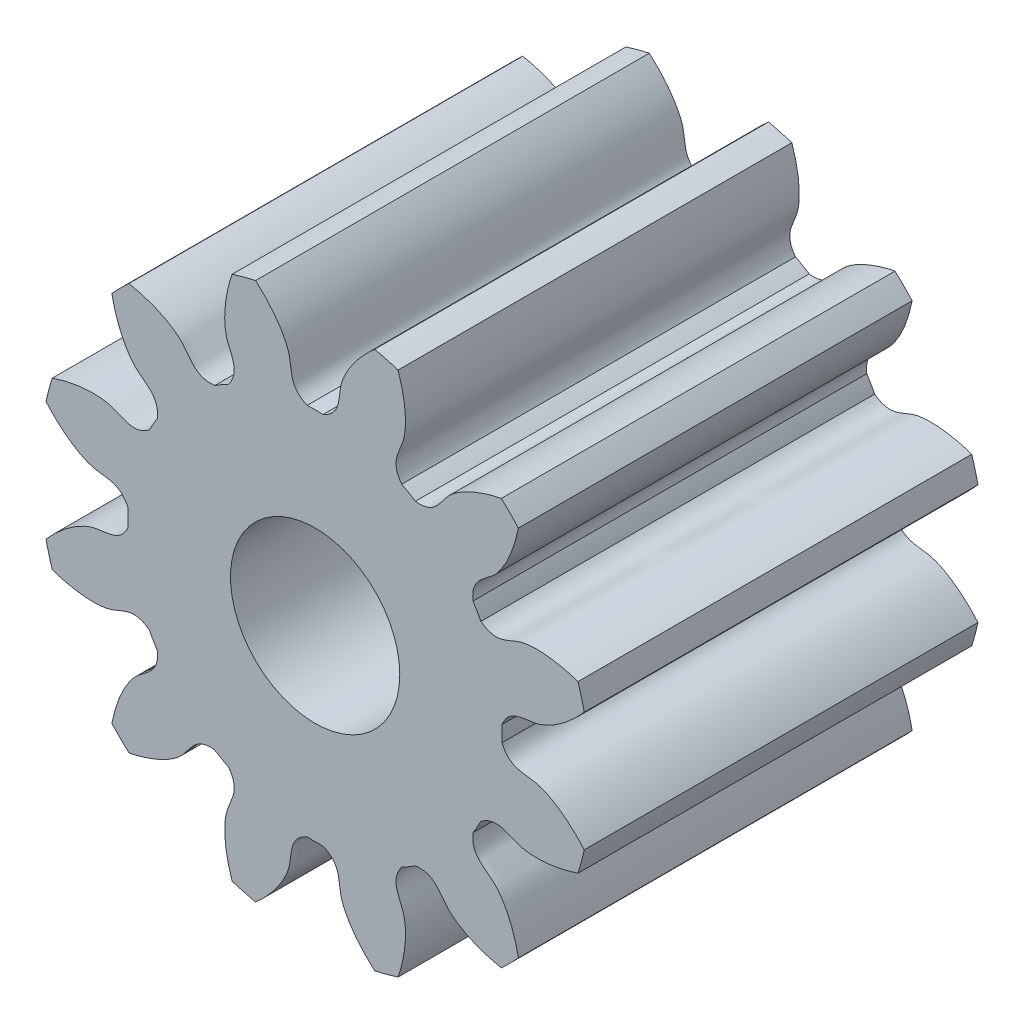
SolidWorks part; units mm, degrees
ref_plane "前视基准面" through (0, 0, 0) normal (0, 0, 1) x (1, 0, 0)
ref_plane "上视基准面" through (0, 0, 0) normal (0, 1, 0) x (1, 0, 0)
ref_plane "右视基准面" through (0, 0, 0) normal (1, 0, 0) x (0, 0, -1)
other "Configuration Table"
sketch "草图1" plane through (0, 0, 0) normal (0, 0, 1) x (1, 0, 0)
  circle A0 centre (0, 0) radius 3.5
extrude "凸台-拉伸1" add sketch "草图1" along normal blind 5
ref_axis "基准轴1" through (0, 0, 5) along (0, 0, -1)
sketch "草图2" plane through (0, 0, 0) normal (0, 0, 1) x (1, 0, 0)
  line L0 (0, 0) -> (0, 3.5) construction
  circle A0 centre (0, 0) radius 3.5 construction
  arc A1 (0.1004, 2.3729) -> (-0.1004, 2.3729) centre (0, 0) ccw
  arc A2 (1.7488, 3.9475) -> (-1.7488, 3.9475) centre (0, 0) ccw
  spline S0 degree 3 poles (0.1004, 2.3729) (0.3404, 2.4747) (0.2872, 2.6724) (0.3381, 2.8447) (0.3413, 2.855) (0.3451, 2.8662) (0.3495, 2.8784) (0.3546, 2.8915) (0.3603, 2.9056) (0.3668, 2.9206) (0.374, 2.9366) (0.3821, 2.9533) (0.3909, 2.971) (0.4007, 2.9894) (0.4114, 3.0086) (0.423, 3.0286) (0.4356, 3.0493) (0.4492, 3.0707) (0.4639, 3.0928) (0.4796, 3.1155) (0.4965, 3.1388) (0.5145, 3.1626) (0.5337, 3.187) (0.554, 3.2119) (0.5756, 3.2372) (0.5985, 3.2629) (0.6226, 3.289) (0.648, 3.3154) (0.6748, 3.342) (0.7028, 3.369) (0.7323, 3.3961) (0.7631, 3.4234) (0.7954, 3.4507) (0.829, 3.4782) (0.8641, 3.5057) (0.9006, 3.5331) (0.9385, 3.5604) (0.978, 3.5877) (1.0189, 3.6147) (1.0613, 3.6416) (1.1052, 3.6681) (1.1506, 3.6944) (1.1975, 3.7203) (1.2459, 3.7457) (1.2958, 3.7707) (1.3472, 3.7952) (1.4001, 3.8191) (1.4546, 3.8424) (1.5105, 3.865) (1.5679, 3.8869) (1.6472, 3.9154) (1.7078, 3.9351) (1.7488, 3.9475) knots 0 0 0 0 0.218015 0.222044 0.226546 0.231522 0.236972 0.242897 0.249295 0.256167 0.263513 0.271332 0.279626 0.288394 0.297636 0.307351 0.317541 0.328204 0.339341 0.350953 0.363038 0.375597 0.38863 0.402137 0.416118 0.430573 0.445502 0.460904 0.476781 0.493132 0.509956 0.527255 0.545027 0.563273 0.581994 0.601188 0.620856 0.640998 0.661614 0.682704 0.704268 0.726305 0.748817 0.771803 0.795262 0.819196 0.843603 0.868484 0.89384 0.919669 0.945972 1 1 1 1
  spline S1 degree 3 poles (-0.1004, 2.3729) (-0.3404, 2.4747) (-0.2872, 2.6724) (-0.3381, 2.8447) (-0.3413, 2.855) (-0.3451, 2.8662) (-0.3495, 2.8784) (-0.3546, 2.8915) (-0.3603, 2.9056) (-0.3668, 2.9206) (-0.374, 2.9366) (-0.3821, 2.9533) (-0.3909, 2.971) (-0.4007, 2.9894) (-0.4114, 3.0086) (-0.423, 3.0286) (-0.4356, 3.0493) (-0.4492, 3.0707) (-0.4639, 3.0928) (-0.4796, 3.1155) (-0.4965, 3.1388) (-0.5145, 3.1626) (-0.5337, 3.187) (-0.554, 3.2119) (-0.5756, 3.2372) (-0.5985, 3.2629) (-0.6226, 3.289) (-0.648, 3.3154) (-0.6748, 3.342) (-0.7028, 3.369) (-0.7323, 3.3961) (-0.7631, 3.4234) (-0.7954, 3.4507) (-0.829, 3.4782) (-0.8641, 3.5057) (-0.9006, 3.5331) (-0.9385, 3.5604) (-0.978, 3.5877) (-1.0189, 3.6147) (-1.0613, 3.6416) (-1.1052, 3.6681) (-1.1506, 3.6944) (-1.1975, 3.7203) (-1.2459, 3.7457) (-1.2958, 3.7707) (-1.3472, 3.7952) (-1.4001, 3.8191) (-1.4546, 3.8424) (-1.5105, 3.865) (-1.5679, 3.8869) (-1.6472, 3.9154) (-1.7078, 3.9351) (-1.7488, 3.9475) knots 0 0 0 0 0.218015 0.222044 0.226546 0.231522 0.236972 0.242897 0.249295 0.256167 0.263513 0.271332 0.279626 0.288394 0.297636 0.307351 0.317541 0.328204 0.339341 0.350953 0.363038 0.375597 0.38863 0.402137 0.416118 0.430573 0.445502 0.460904 0.476781 0.493132 0.509956 0.527255 0.545027 0.563273 0.581994 0.601188 0.620856 0.640998 0.661614 0.682704 0.704268 0.726305 0.748817 0.771803 0.795262 0.819196 0.843603 0.868484 0.89384 0.919669 0.945972 1 1 1 1
extrude "切除-拉伸1" cut sketch "草图2" along normal through all
pattern_circular "阵列(圆周)1" count 12 over 360 about axis through (0, 0, 5) along (0, 0, -1) of "切除-拉伸1"
sketch "草图3" plane through (0, 0, 0) normal (0, 0, 1) x (1, 0, 0)
  circle A0 centre (0, 0) radius 3 construction
  dimension "Dn" = 6
sketch "草图4" plane through (0, 0, 5) normal (0, 0, 1) x (1, 0, 0)
  circle A0 centre (0, 0) radius 1.075
  dimension "D1" = 2.15
extrude "切除-拉伸2" cut sketch "草图4" against normal up to next
